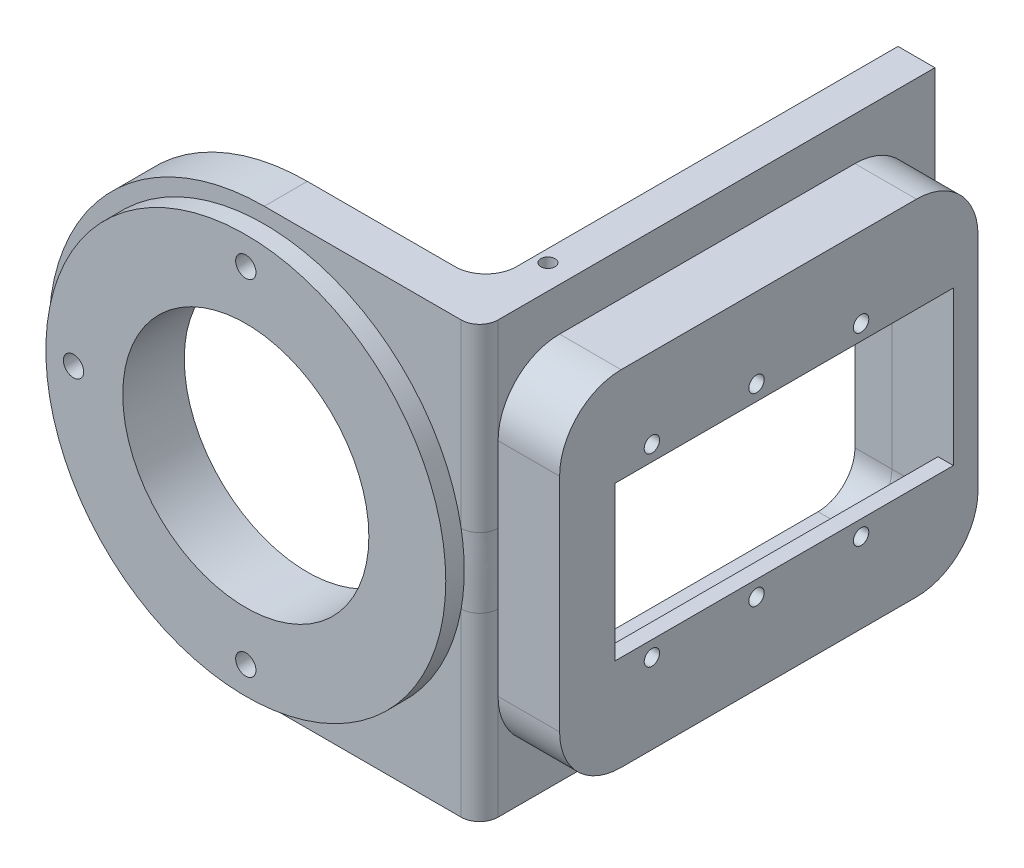
SolidWorks part; units mm, degrees
ref_plane "Front Plane" through (0, 0, 0) normal (0, 0, 1) x (1, 0, 0)
ref_plane "Top Plane" through (0, 0, 0) normal (0, 1, 0) x (1, 0, 0)
ref_plane "Right Plane" through (0, 0, 0) normal (1, 0, 0) x (0, 0, -1)
sketch "Sketch1" plane through (0, 0, 0) normal (0, 0, 1) x (1, 0, 0)
  circle A5 centre (0, 0) radius 32.5
  dimension "D1" = 65
extrude "Boss-Extrude1" add sketch "Sketch1" against normal blind 3
ref_plane "Plane1" through (45, 0, 0) normal (1, 0, 0) x (0, 0, -1)
sketch "Sketch10" plane through (0, 0, -3) normal (0, 0, -1) x (-1, 0, 0)
  line L1 (-35, -35) -> (35, -35)
  line L2 (-35, -35) -> (-35, 35)
  line L3 (-35, 35) -> (35, 35)
  line L4 (35, -35) -> (35, 35)
  line L5 (-35, -35) -> (35, 35) construction
  line L6 (-35, 35) -> (35, -35) construction
  point P0 (0, 0)
  dimension "D1" = 70
  dimension "D2" = 70
extrude "Boss-Extrude6" add sketch "Sketch10" along normal blind 74
sketch "Sketch2" plane through (45, 0, 0) normal (1, 0, 0) x (0, 0, -1)
  line L2 (0, 0) -> (146.6861, 0) construction
  line L3 (40, 0) -> (40, 30) construction
  line L5 (3, 35) -> (3, -35) construction
  line L6 (77, 35) -> (77, -35) construction
  line L7 (16, -28) -> (64, -28)
  line L8 (6, -18) -> (6, 18)
  line L9 (16, 28) -> (64, 28)
  line L10 (74, -18) -> (74, 18)
  line L11 (6, -28) -> (74, 28) construction
  line L12 (6, 28) -> (74, -28) construction
  arc A1 (16, -28) -> (6, -18) centre (16, -18) cw
  arc A2 (64, -28) -> (74, -18) centre (64, -18) ccw
  arc A3 (64, 28) -> (74, 18) centre (64, 18) cw
  arc A4 (6, 18) -> (16, 28) centre (16, 18) cw
  point P0 (77, 0)
  dimension "D1" = 68
  dimension "D3" = 10
  dimension "D2" = 56
extrude "Boss-Extrude2" add sketch "Sketch2" against normal up to surface (10 mm away) separate body up to face at (35, 0, -40)
sketch "Sketch11" plane through (0, 35, 0) normal (0, 1, 0) x (1, 0, 0)
  line L1 (-35, 77) -> (29, 77)
  line L2 (-35, 77) -> (-35, 10)
  line L3 (-35, 10) -> (29, 10)
  line L4 (29, 77) -> (29, 10)
  dimension "D1" = 67
  dimension "D2" = 64
extrude "Cut-Extrude5" cut sketch "Sketch11" against normal through all
sketch "Sketch4" plane through (35, 0, 0) normal (-1, 0, 0) x (0, 0, 1)
  line L8 (-64, -24) -> (-16, -24)
  line L9 (-70, 18) -> (-70, -18)
  line L10 (-16, 24) -> (-64, 24)
  line L11 (-10, -18) -> (-10, 18)
  line L12 (-64, -24) -> (-16, -24)
  line L13 (-70, 18) -> (-70, -18)
  line L14 (-16, 24) -> (-64, 24)
  line L15 (-10, -18) -> (-10, 18)
  arc A10 (-70, -18) -> (-64, -24) centre (-64, -18) ccw
  arc A11 (-64, 24) -> (-70, 18) centre (-64, 18) ccw
  arc A12 (-10, 18) -> (-16, 24) centre (-16, 18) ccw
  arc A13 (-16, -24) -> (-10, -18) centre (-16, -18) ccw
  arc A14 (-70, -18) -> (-64, -24) centre (-64, -18) ccw
  arc A15 (-64, 24) -> (-70, 18) centre (-64, 18) ccw
  arc A16 (-10, 18) -> (-16, 24) centre (-16, 18) ccw
  arc A17 (-16, -24) -> (-10, -18) centre (-16, -18) ccw
  dimension "D1" = 4
extrude "Cut-Extrude2" cut sketch "Sketch4" against normal through all contours L12 A17 L15 A16 L14 A15 L13 A14 region at (35, 0, -40)
sketch "Sketch5" plane through (45, 0, 0) normal (1, 0, 0) x (0, 0, -1)
  line L0 (45, 0) -> (10, 0) construction
  line L1 (70, 18) -> (70, 12.5)
  line L2 (70, 12.5) -> (15, 12.5)
  line L3 (15, 12.5) -> (15, -12.5)
  line L4 (15, -12.5) -> (70, -12.5)
  line L5 (70, -12.5) -> (70, -18)
  line L10 (45, 0) -> (45, -15) construction
  line L11 (45, -15) -> (38, -15) construction
  line L12 (38, -15) -> (35, -15) construction
  line L13 (35, -15) -> (21, -15) construction
  line L14 (70, 18) -> (70, -18) construction
  line L15 (10, 18) -> (10, -18)
  line L18 (10, -18) -> (10, 18) construction
  line L19 (16, 24) -> (64, 24) construction
  line L20 (16, 24) -> (64, 24)
  line L21 (64, -24) -> (16, -24) construction
  line L22 (64, -24) -> (16, -24)
  line L23 (55, -15) -> (38, -15) construction
  circle A0 centre (45, 0) radius 11 construction
  circle A1 centre (55, 15) radius 1.25
  circle A2 centre (38, -15) radius 1.25
  arc A3 (16, 24) -> (10, 18) centre (16, 18) ccw
  circle A6 centre (21, -15) radius 1.25
  circle A7 centre (38, 15) radius 1.25
  circle A9 centre (21, 15) radius 1.25
  arc A10 (10, -18) -> (16, -24) centre (16, -18) ccw
  arc A11 (70, 18) -> (64, 24) centre (64, 18) ccw construction
  arc A12 (70, 18) -> (64, 24) centre (64, 18) ccw
  arc A13 (64, -24) -> (70, -18) centre (64, -18) ccw construction
  arc A14 (64, -24) -> (70, -18) centre (64, -18) ccw
  circle A15 centre (55, -15) radius 1.25
  point P8 (15, 0)
  point P14 (0, 0)
  point P33 (0, 0)
  point P34 (0, 0)
  dimension "D1" = 22
  dimension "D6" = 2.5
  dimension "D3" = 25
  dimension "D4" = 15
  dimension "D5" = 7
  dimension "D7" = 17
  dimension "D8" = 17
  dimension "D10" = 5
  dimension "D2" = 30
extrude "Boss-Extrude3" add sketch "Sketch5" against normal blind 2.5
sketch "Sketch13" plane through (35, 0, 0) normal (1, 0, 0) x (0, 0, -1)
  line L4 (10, 18) -> (10, -18)
  line L5 (16, -24) -> (64, -24)
  line L6 (70, -18) -> (70, 18)
  line L7 (64, 24) -> (16, 24)
  line L8 (10, 18) -> (10, -18)
  line L9 (16, -24) -> (64, -24)
  line L10 (70, -18) -> (70, 18)
  line L11 (64, 24) -> (16, 24)
  arc A6 (16, 24) -> (10, 18) centre (16, 18) ccw
  arc A7 (10, -18) -> (16, -24) centre (16, -18) ccw
  arc A8 (64, -24) -> (70, -18) centre (64, -18) ccw
  arc A9 (70, 18) -> (64, 24) centre (64, 18) ccw
  arc A10 (16, 24) -> (10, 18) centre (16, 18) ccw
  arc A11 (10, -18) -> (16, -24) centre (16, -18) ccw
  arc A12 (64, -24) -> (70, -18) centre (64, -18) ccw
  arc A13 (70, 18) -> (64, 24) centre (64, 18) ccw
  dimension "D1" = 0
extrude "Cut-Extrude6" cut sketch "Sketch13" against normal up to surface (6 mm away) up to face at (29, 0, -43.5)
sketch "Sketch14" plane through (0, 0, 0) normal (0, 0, 1) x (1, 0, 0)
  line L0 (29, -18) -> (-35, -35) construction
  line L2 (29, -35) -> (29, -18) construction
  line L3 (29, -35) -> (29, -18) construction
  circle A2 centre (0, 0) radius 32.5
  circle A3 centre (0, 0) radius 28.5
  circle A4 centre (0, 0) radius 32.5 construction
  dimension "D1" = 0
sketch "Sketch16" plane through (45, 0, 0) normal (1, 0, 0) x (0, 0, -1)
  circle A0 centre (38, -15) radius 2.25
  circle A2 centre (21, -15) radius 2.25
  circle A3 centre (21, 15) radius 2.25
  circle A5 centre (38, 15) radius 2.25
  dimension "D1" = 4.5
extrude "Cut-Extrude8" [suppressed] cut sketch "Sketch16" against normal blind 2.5
fillet "Fillet1" radius 3 1 edges at (35, 0, -3)
fillet "Fillet2" [suppressed] radius 10
sketch "Sketch17" plane through (0, 0, -10) normal (0, 0, -1) x (-1, 0, 0)
  line L0 (-28, 0) -> (0, 0) construction
  line L1 (0, 28) -> (0, 0) construction
  line L2 (28, 0) -> (0, 0) construction
  line L3 (0, -28) -> (0, 0) construction
  circle A0 centre (-28, 0) radius 1.65 construction
  circle A1 centre (0, 28) radius 1.65
  circle A2 centre (28, 0) radius 1.65
  circle A3 centre (0, -28) radius 1.65
  circle A5 centre (0, 0) radius 28.5
  circle A6 centre (0, 0) radius 28.5 construction
  point P10 (0, 0)
  point P17 (0, 0)
  dimension "D4" = 3.3
  dimension "D3" = 28
  dimension "D5" = 0
  dimension "D1" = 4
  dimension "D2" = 4
extrude "Cut-Extrude9" cut sketch "Sketch17" against normal through all
sketch "Sketch19" plane through (29, 0, 0) normal (-1, 0, 0) x (0, 0, 1)
  line L0 (-71, 35) -> (-71, -35) construction
  line L1 (-10, 35) -> (-77, 35) construction
  line L2 (-10, -35) -> (-77, -35) construction
  line L3 (-77, -35) -> (-77, 35) construction
  line L4 (-71, 28) -> (-73, 28)
  line L5 (-71, 28) -> (-71, 23.8)
  line L6 (-71, 23.8) -> (-73, 23.8)
  line L7 (-73, 28) -> (-73, 23.8)
  line L8 (-71, -23.8) -> (-73, -23.8)
  line L9 (-71, -23.8) -> (-71, -28)
  line L10 (-71, -28) -> (-73, -28)
  line L11 (-73, -23.8) -> (-73, -28)
  line L12 (-71, 0) -> (-77, 0) construction
  dimension "D1" = 6
  dimension "D2" = 7
  dimension "D3" = 2
  dimension "D4" = 4.2
extrude "Cut-Extrude10" cut sketch "Sketch19" along direction (1, 0, 0) on the side against the normal blind 4
sketch "Sketch21" plane through (0, 0, -10) normal (0, 0, -1) x (-1, 0, 0)
  line L0 (29, 35) -> (29, -35) construction
  line L1 (31, 28) -> (29, 28)
  line L2 (31, 28) -> (31, 23.8)
  line L3 (31, 23.8) -> (29, 23.8)
  line L4 (29, 28) -> (29, 23.8)
  line L5 (31, -23.8) -> (29, -23.8)
  line L6 (31, -23.8) -> (31, -28)
  line L7 (31, -28) -> (29, -28)
  line L8 (29, -23.8) -> (29, -28)
  line L9 (29, 0) -> (35, 0) construction
  line L10 (35, -35) -> (35, 35) construction
  line L11 (35, 35) -> (-29, 35) construction
  dimension "D1" = 2
  dimension "D2" = 4.2
  dimension "D3" = 7
  dimension "D4" = 6
extrude "Cut-Extrude11" cut sketch "Sketch21" against normal blind 4
sketch "Sketch22" plane through (0, 0, -77) normal (0, 0, -1) x (-1, 0, 0)
  line L0 (-29, 28) -> (-33, 23.8) construction
  line L1 (-29, -23.8) -> (-33, -28) construction
  line L4 (-29, 23.8) -> (-29, 28)
  line L5 (-29, 28) -> (-33, 28)
  line L6 (-33, 28) -> (-33, 23.8)
  line L7 (-33, 23.8) -> (-29, 23.8)
  line L8 (-29, 23.8) -> (-29, 28) construction
  line L9 (-29, 28) -> (-33, 28) construction
  line L11 (-33, 23.8) -> (-29, 23.8) construction
  line L12 (-29, -28) -> (-29, -23.8)
  line L13 (-29, -23.8) -> (-33, -23.8)
  line L14 (-33, -23.8) -> (-33, -28)
  line L15 (-33, -28) -> (-29, -28)
  line L16 (-29, -28) -> (-29, -23.8) construction
  line L17 (-29, -23.8) -> (-33, -23.8) construction
  line L19 (-33, -28) -> (-29, -28) construction
  line L22 (-33, 28) -> (-33, 23.8)
  line L23 (-33, -23.8) -> (-33, -28)
  circle A0 centre (-31, 25.9) radius 1.15
  circle A1 centre (-31, -25.9) radius 1.15
  dimension "D3" = 2.3
  dimension "D1" = 0
  dimension "D2" = 0
extrude "Cut-Extrude12" cut sketch "Sketch22" against normal up to surface (4 mm away) contours A0 | A1 region at (31, 25.9, -77) region at (31, -25.9, -77) up to face at (31, 25.9, -73)
sketch "Sketch23" plane through (-35, 0, 0) normal (-1, 0, 0) x (0, 0, 1)
  line L0 (-10, -28) -> (-6, -23.8) construction
  line L1 (-10, 23.8) -> (-6, 28) construction
  line L4 (-10, -23.8) -> (-10, -28)
  line L5 (-10, -28) -> (-6, -28)
  line L6 (-6, -28) -> (-6, -23.8)
  line L7 (-6, -23.8) -> (-10, -23.8)
  line L8 (-10, -23.8) -> (-10, -28) construction
  line L9 (-10, -28) -> (-6, -28) construction
  line L11 (-6, -23.8) -> (-10, -23.8) construction
  line L12 (-10, 28) -> (-10, 23.8)
  line L13 (-10, 23.8) -> (-6, 23.8)
  line L14 (-6, 23.8) -> (-6, 28)
  line L15 (-6, 28) -> (-10, 28)
  line L16 (-10, 28) -> (-10, 23.8) construction
  line L17 (-10, 23.8) -> (-6, 23.8) construction
  line L19 (-6, 28) -> (-10, 28) construction
  line L22 (-6, -28) -> (-6, -23.8)
  line L23 (-6, 23.8) -> (-6, 28)
  circle A0 centre (-8, -25.9) radius 1.15
  circle A1 centre (-8, 25.9) radius 1.15
  dimension "D3" = 2.3
  dimension "D1" = 0
  dimension "D2" = 0
sketch "Sketch24" plane through (0, 0, -10) normal (0, 0, -1) x (-1, 0, 0)
  circle A0 centre (0, 0) radius 20
  circle A2 centre (0, 0) radius 28.5
  circle A3 centre (0, 0) radius 28.5 construction
  dimension "D1" = 40
  dimension "D2" = 0
extrude "Cut-Extrude14" cut sketch "Sketch24" against normal up to surface (10 mm away) up to face at (-1.65, 28, 0)
fillet "Fillet4" radius 5 2 edges at (29, 26.5, -10) (29, -26.5, -10)
fillet "Fillet6" radius 35 2 edges at (-35, -35, -6.5) (-35, 35, -6.5)
sketch "Sketch25" plane through (29, 0, 19) normal (-1, 0, 0) x (0, 0, 1)
  line L1 (-39.2, -29) -> (-39.2, -31)
  line L2 (-39.2, -29) -> (-35, -29)
  line L3 (-35, -29) -> (-35, -31)
  line L4 (-39.2, -31) -> (-35, -31)
  line L9 (-29, -18) -> (-29, -35) construction
  line L11 (-96, -35) -> (-25, -35) construction
  dimension "D1" = 2
  dimension "D2" = 4.2
  dimension "D3" = 6
  dimension "D4" = 6
extrude "Cut-Extrude15" cut sketch "Sketch25" against normal blind 4
ref_plane "Plane2" through (0, 0, 0) normal (0, -1, 0) x (-1, 0, 0)
sketch "Sketch26" plane through (0, -29, 0) normal (0, -1, 0) x (1, 0, 0)
  line L0 (33, -20.2) -> (29, -16) construction
  circle A0 centre (31, -18.1) radius 1.15
  dimension "D1" = 2.3
extrude "Cut-Extrude16" cut sketch "Sketch26" along normal blind 10
mirror "Mirror1" about plane through (0, 0, 0) normal (0, -1, 0) of "Cut-Extrude15", "Cut-Extrude16"
